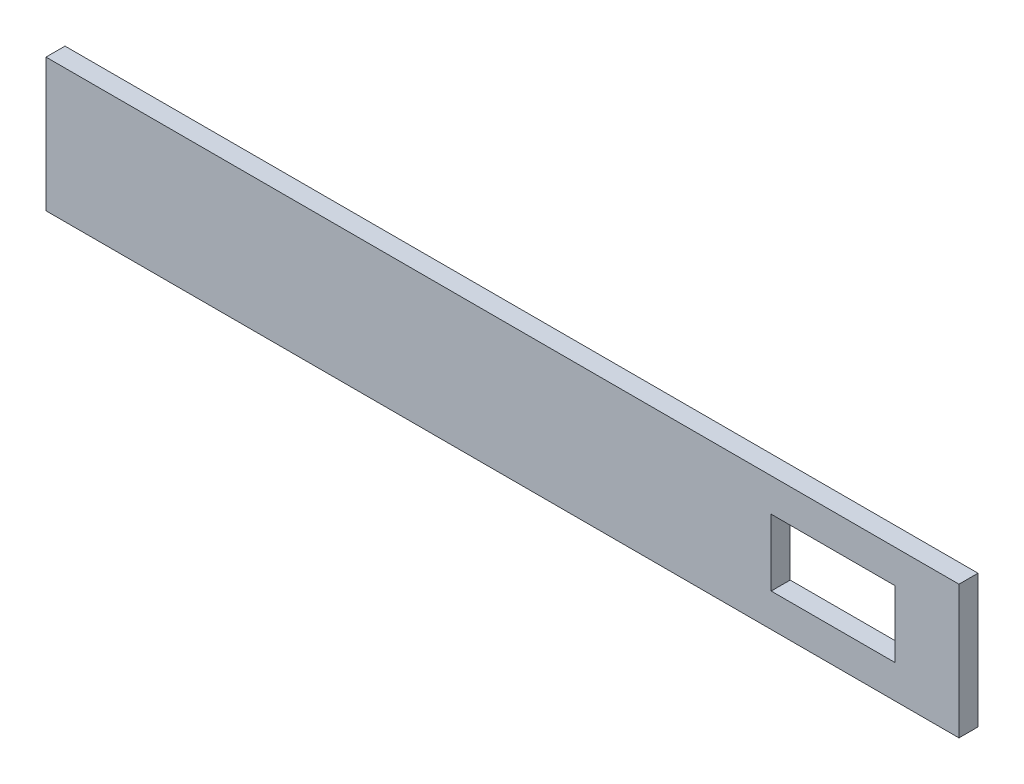
SolidWorks part; units mm, degrees
ref_plane "Front Plane" through (0, 0, 0) normal (0, 0, 1) x (1, 0, 0)
ref_plane "Top Plane" through (0, 0, 0) normal (0, 1, 0) x (1, 0, 0)
ref_plane "Right Plane" through (0, 0, 0) normal (1, 0, 0) x (0, 0, -1)
sketch "Sketch1" plane through (0, 0, 0) normal (0, 0, 1) x (1, 0, 0)
  line L0 (-262.733, -54.9538) -> (-262.733, 69.85) construction
  line L1 (42.067, 22.225) -> (-262.733, 22.225)
  line L2 (42.067, 22.225) -> (42.067, -22.225)
  line L3 (42.067, -22.225) -> (-262.733, -22.225)
  line L4 (-262.733, 22.225) -> (-262.733, -22.225)
  line L5 (63.0291, 0) -> (-62.7737, 0) construction
  line L6 (-19.6295, 10.033) -> (19.6295, 10.033) construction
  line L7 (19.6295, -10.033) -> (-19.6295, -10.033) construction
  line L8 (27.25, 6.27) -> (27.25, 8.0899) construction
  dimension "D1" = 44.45
  dimension "D2" = 14.817
extrude "Boss-Extrude1" add sketch "Sketch1" along normal blind 6.35
sketch "Sketch2" plane through (0, 0, 6.35) normal (0, 0, 1) x (1, 0, 0)
  line L0 (-41.9443, 0) -> (30.2812, 0) construction
  line L1 (-20.6375, 11.1125) -> (20.6375, 11.1125)
  line L2 (-20.6375, 11.1125) -> (-20.6375, -11.1125)
  line L3 (-20.6375, -11.1125) -> (20.6375, -11.1125)
  line L4 (20.6375, 11.1125) -> (20.6375, -11.1125)
  line L5 (-19.6295, 10.033) -> (19.6295, 10.033) construction
  line L6 (19.6295, -10.033) -> (-19.6295, -10.033) construction
  line L7 (0, 34.6052) -> (0, -28.4279) construction
  line L8 (-20.1295, -9.533) -> (-20.1295, 9.533) construction
  line L9 (20.1295, 9.533) -> (20.1295, -9.533) construction
  dimension "D1" = 22.225
  dimension "D2" = 41.275
extrude "Cut-Extrude1" cut sketch "Sketch2" against normal through all
